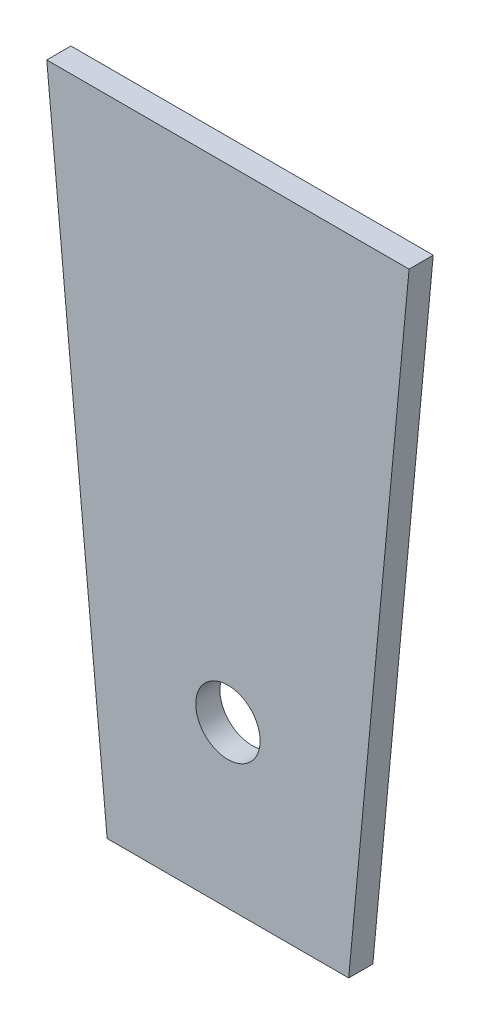
SolidWorks part; units mm, degrees
material "7075-O (SS)"
ref_plane "Front Plane" through (0, 0, 0) normal (0, 0, 1) x (1, 0, 0)
ref_plane "Top Plane" through (0, 0, 0) normal (0, 1, 0) x (1, 0, 0)
ref_plane "Right Plane" through (0, 0, 0) normal (1, 0, 0) x (0, 0, -1)
sketch "Sketch1" plane through (0, 0, 0) normal (0, 0, 1) x (1, 0, 0)
  line L0 (-22.5, 80) -> (22.5, 80)
  line L1 (-15, 0) -> (15, 0)
  line L2 (-22.5, 80) -> (-15, 0)
  line L3 (22.5, 80) -> (15, 0)
  circle A0 centre (0, 20) radius 4
  point P6 (0, 0)
  dimension "D5" = 8
  dimension "D6" = 20
  dimension "D7" = 22.5
  dimension "D1" = 45
  dimension "D2" = 80
  dimension "D3" = 22.5
  dimension "D4" = 30
extrude "Boss-Extrude1" add sketch "Sketch1" along normal blind 3
